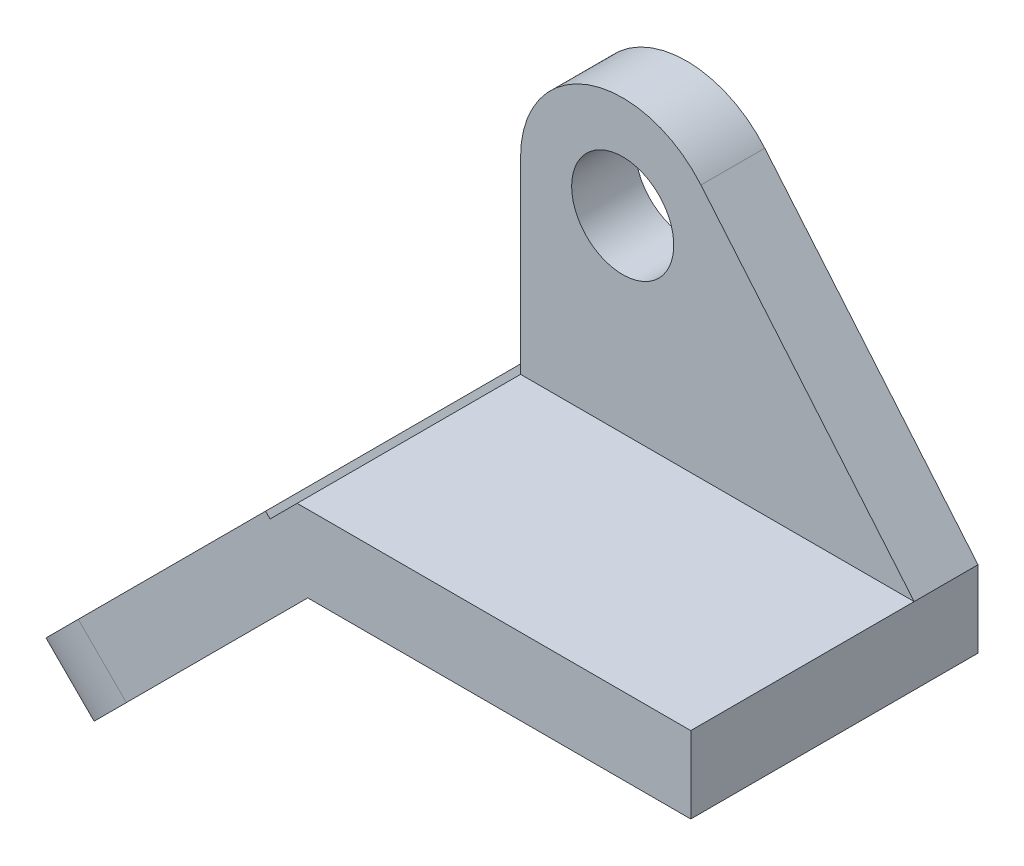
SolidWorks part; units mm, degrees
ref_plane "前视基准面" through (0, 0, 0) normal (0, 0, 1) x (1, 0, 0)
ref_plane "上视基准面" through (0, 0, 0) normal (0, 1, 0) x (1, 0, 0)
ref_plane "右视基准面" through (0, 0, 0) normal (1, 0, 0) x (0, 0, -1)
other "Configuration Table"
sketch "草图2" plane through (0, 0, 0) normal (0, 0, 1) x (1, 0, 0)
  line L0 (0, 0) -> (60, 0)
  line L1 (60, 0) -> (60, 12)
  line L2 (60, 12) -> (-1.6611, 12)
  line L3 (-1.6611, 12) -> (-5.9038, 7.7574)
  line L4 (-5.9038, 7.7574) -> (-6.6109, 8.4645)
  line L5 (-6.6109, 8.4645) -> (-51.8606, -36.7853)
  line L6 (0, 0) -> (-44.323, -44.323)
  line L7 (-44.323, -44.323) -> (-51.8606, -36.7853)
  dimension "D1" = 135
  dimension "D2" = 60
  dimension "D3" = 12
  dimension "D4" = 6
  dimension "D5" = 1
  dimension "D6" = 70
extrude "凸台-拉伸1" add sketch "草图2" along normal blind 45
sketch "草图3" plane through (0, 0, 0) normal (0, 0, -1) x (-1, 0, 0)
  line L0 (-60, 12) -> (-26.5956, 51.8098)
  line L1 (-60, 12) -> (1.6611, 12)
  line L2 (1.6611, 12) -> (1.6611, 41.5252)
  circle A0 centre (-14.3389, 41.5252) radius 8
  arc A2 (1.6611, 41.5252) -> (-26.5956, 51.8098) centre (-14.3389, 41.5252) ccw
  point P1 (-12.8842, 32.6036)
  dimension "D2" = 32
  dimension "D3" = 16
  dimension "D1" = 50
extrude "凸台-拉伸2" add sketch "草图3" against normal blind 10
fillet "圆角1" 2 edges at (-48.0918, -40.5541, 45) (-48.0918, -40.5541, 0) type full round first side face at (1.2051, -5.1108, 45) second side face at (3.0974, 6.2341, 0) middle face at (-48.0918, -40.5541, 22.5)
sketch "草图6" plane through (-7.5377, 7.5377, 0) normal (-0.7071, 0.7071, 0) x (0, 0, 1)
  line L0 (22.5, -20.1822) -> (22.5, -40.1822) construction
  line L1 (30.5, -20.1822) -> (30.5, -40.1822)
  line L2 (14.5, -20.1822) -> (14.5, -40.1822)
  line L3 (0, 1.3107) -> (0, -40.1822)
  line L4 (45, -40.1822) -> (45, 1.3107)
  line L5 (45, 1.3107) -> (0, 1.3107)
  line L6 (0, 1.3107) -> (0, -40.1822)
  line L7 (45, -40.1822) -> (45, 1.3107)
  line L8 (45, 1.3107) -> (0, 1.3107)
  arc A0 (30.5, -20.1822) -> (14.5, -20.1822) centre (22.5, -20.1822) ccw
  arc A1 (0, -40.1822) -> (45, -40.1822) centre (22.5, -40.1822) ccw
  arc A2 (0, -40.1822) -> (45, -40.1822) centre (22.5, -40.1822) ccw
  arc A3 (14.5, -40.1822) -> (30.5, -40.1822) centre (22.5, -40.1822) ccw
  point P5 (22.5, -30.1822)
  dimension "D2" = 20
  dimension "D3" = 16
  dimension "D1" = 0
extrude "切除-拉伸1" cut sketch "草图6" against normal through all both and the other way through all contours L2 A3 L1 A0
